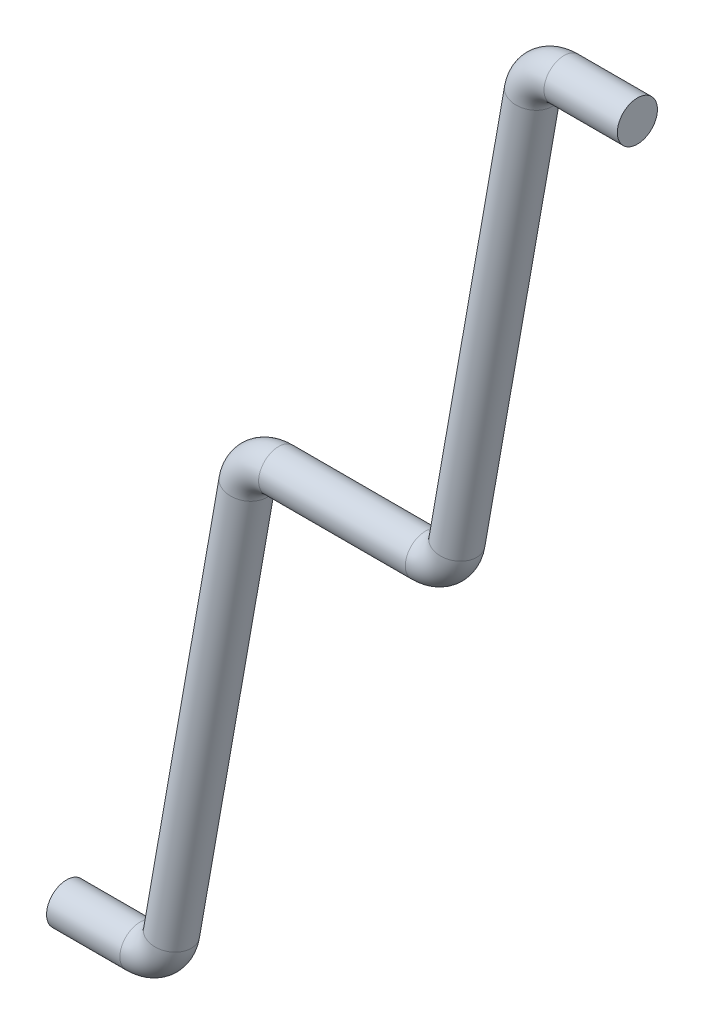
SolidWorks part; units mm, degrees
ref_plane "Front" through (0, 0, 0) normal (0, 0, 1) x (1, 0, 0)
ref_plane "Top" through (0, 0, 0) normal (0, 1, 0) x (1, 0, 0)
ref_plane "Right" through (0, 0, 0) normal (1, 0, 0) x (0, 0, -1)
sketch "Sketch4" plane through (0, 0, 0) normal (1, 0, 0) x (0, 0, -1)
  circle A0 centre (0, 0) radius 6.35
  dimension "D1" = 12.7
sketch "Sketch5" plane through (0, 0, 0) normal (0, 0, 1) x (1, 0, 0)
  line L0 (0, 0) -> (23.2247, 0)
  line L1 (33.2304, 8.3957) -> (57.1418, 144.0043)
  line L2 (67.1475, 152.4) -> (90.3722, 152.4)
  line L3 (90.3722, 152.4) -> (90.3722, 211.8411) construction
  line L4 (90.3722, 152.4) -> (113.597, 152.4)
  line L5 (123.6026, 160.7957) -> (147.5141, 296.4043)
  line L6 (157.5197, 304.8) -> (180.7445, 304.8)
  arc A0 (157.5197, 304.8) -> (147.5141, 296.4043) centre (157.5197, 294.64) ccw
  arc A1 (123.6026, 160.7957) -> (113.597, 152.4) centre (113.597, 162.56) cw
  arc A2 (67.1475, 152.4) -> (57.1418, 144.0043) centre (67.1475, 142.24) ccw
  arc A3 (33.2304, 8.3957) -> (23.2247, 0) centre (23.2247, 10.16) cw
  point P11 (148.9945, 304.8)
  point P14 (122.1222, 152.4)
  point P17 (58.6222, 152.4)
  point P20 (31.75, 0)
  dimension "D7" = 10.16
  dimension "D1" = 31.75
  dimension "D2" = 152.4
  dimension "D3" = 31.75
  dimension "D4" = 100
  dimension "D5" = 63.5
  dimension "D6" = 31.75
sweep "Sweep3" add profiles "Sketch4" path "Sketch5"
